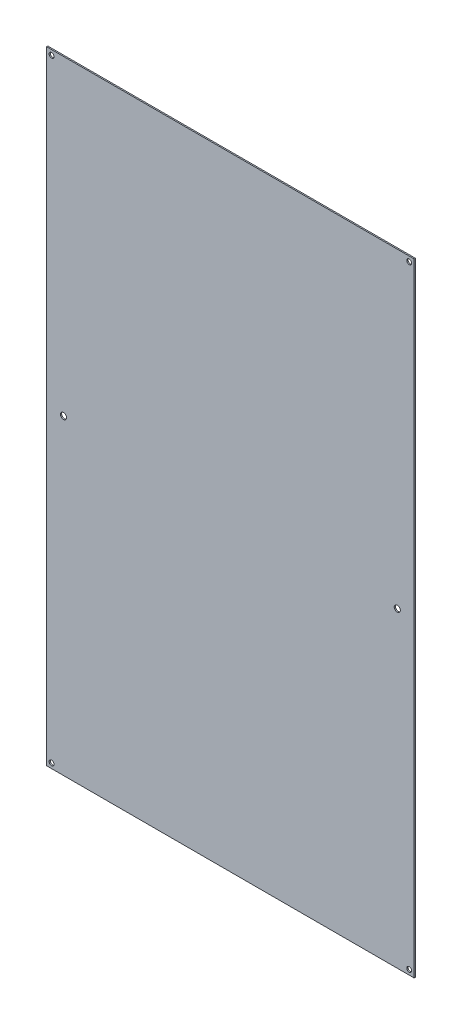
SolidWorks part; units mm, degrees
ref_plane "Front Plane" through (0, 0, 0) normal (0, 0, 1) x (1, 0, 0)
ref_plane "Top Plane" through (0, 0, 0) normal (0, 1, 0) x (1, 0, 0)
ref_plane "Right Plane" through (0, 0, 0) normal (1, 0, 0) x (0, 0, -1)
sketch "Sketch2" plane through (0, 0, 0) normal (0, 0, 1) x (1, 0, 0)
  line L0 (108.8476, 918.9814) -> (-369.1524, 918.9814)
  line L1 (109.8476, 919.9814) -> (-370.1524, 919.9814) construction
  line L2 (109.8476, 919.9814) -> (109.8476, 108.0813) construction
  line L3 (109.8476, 108.0813) -> (-370.1524, 108.0813) construction
  line L4 (-370.1524, 919.9814) -> (-370.1524, 108.0813) construction
  line L5 (-369.1524, 918.9814) -> (-369.1524, 109.0813)
  line L6 (108.8476, 109.0813) -> (-369.1524, 109.0813)
  line L7 (108.8476, 918.9814) -> (108.8476, 109.0813)
  circle A0 centre (-362.7102, 115.5224) radius 3.175 construction
  circle A1 centre (-362.7102, 115.5224) radius 3.175
  circle A2 centre (102.4054, 912.5404) radius 3.175 construction
  circle A3 centre (-362.7102, 912.5404) radius 3.175 construction
  circle A4 centre (102.4054, 115.5224) radius 3.175 construction
  circle A5 centre (102.4054, 912.5404) radius 3.175
  circle A6 centre (-362.7102, 912.5404) radius 3.175
  circle A7 centre (102.4054, 115.5224) radius 3.175
  circle A8 centre (86.8936, 514.0313) radius 3.9687 construction
  circle A9 centre (-347.1984, 514.0313) radius 3.9687 construction
  circle A10 centre (86.8936, 514.0313) radius 3.9687
  circle A11 centre (-347.1984, 514.0313) radius 3.9687
  dimension "\"Panel_Offset\"" = 1
extrude "Boss-Extrude1" add sketch "Sketch2" along normal blind 1.6002
